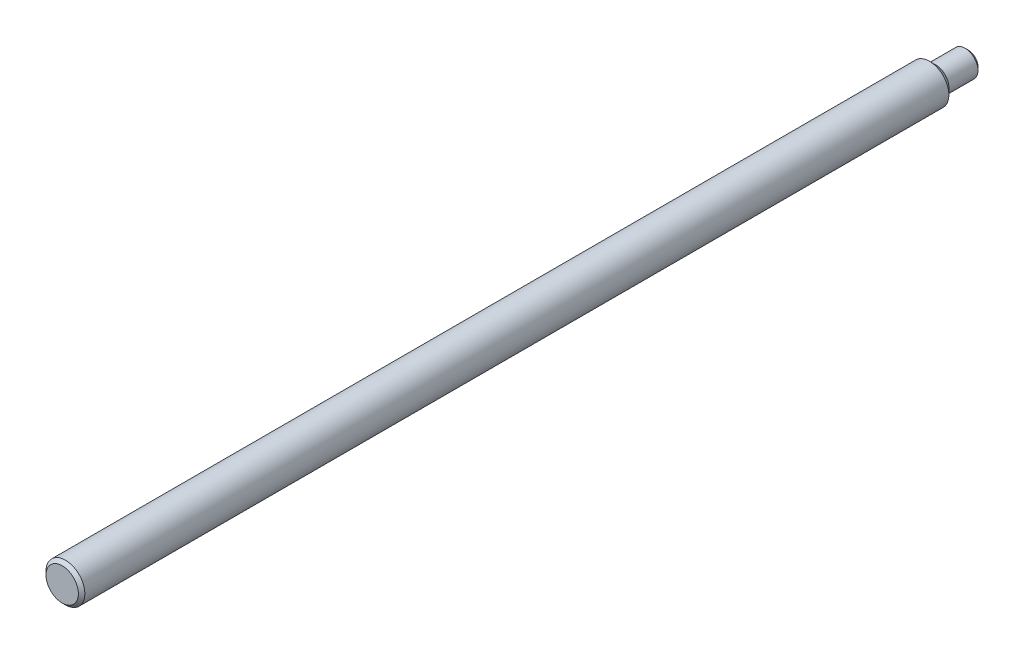
SolidWorks part; units mm, degrees
ref_plane "Piano frontale" through (0, 0, 0) normal (0, 0, 1) x (1, 0, 0)
ref_plane "Piano superiore" through (0, 0, 0) normal (0, 1, 0) x (1, 0, 0)
ref_plane "Piano destro" through (0, 0, 0) normal (1, 0, 0) x (0, 0, -1)
sketch "Schizzo1" plane through (0, 0, 0) normal (0, 0, 1) x (1, 0, 0)
  circle A0 centre (0, 0) radius 6
  dimension "D1" = 12
extrude "Estrusione-Estrusione1" add sketch "Schizzo1" along normal blind 280
cosmetic thread "Filettatura cosmetica1" parameters "D2"=10.344
sketch "Schizzo2" plane through (0, 0, 0) normal (0, 1, 0) x (1, 0, 0)
  line L0 (0, 1.8987) -> (0, -61.2971) construction
  line L1 (-4, -10) -> (-6, -12)
  line L2 (-6, -12) -> (-6, 0)
  line L3 (-6, 0) -> (-4, 0)
  line L4 (-4, 0) -> (-4, -10)
  line L5 (-6, 0) -> (-6, -280) construction
  line L6 (6, 0) -> (-6, 0) construction
  dimension "D1" = 8
  dimension "D2" = 135
  dimension "D3" = 10
revolve "Taglia-Rivoluzione1" cut sketch "Schizzo2" angle 360 about L0
chamfer "Smusso1" distance 1 angle 45 2 edges at (-4, 0, 0) (6, 0, 280)
sketch "Schizzo3" plane through (0, 0, 0) normal (0, 1, 0) x (1, 0, 0)
  line L0 (-4, -10) -> (-4, -10.2926)
